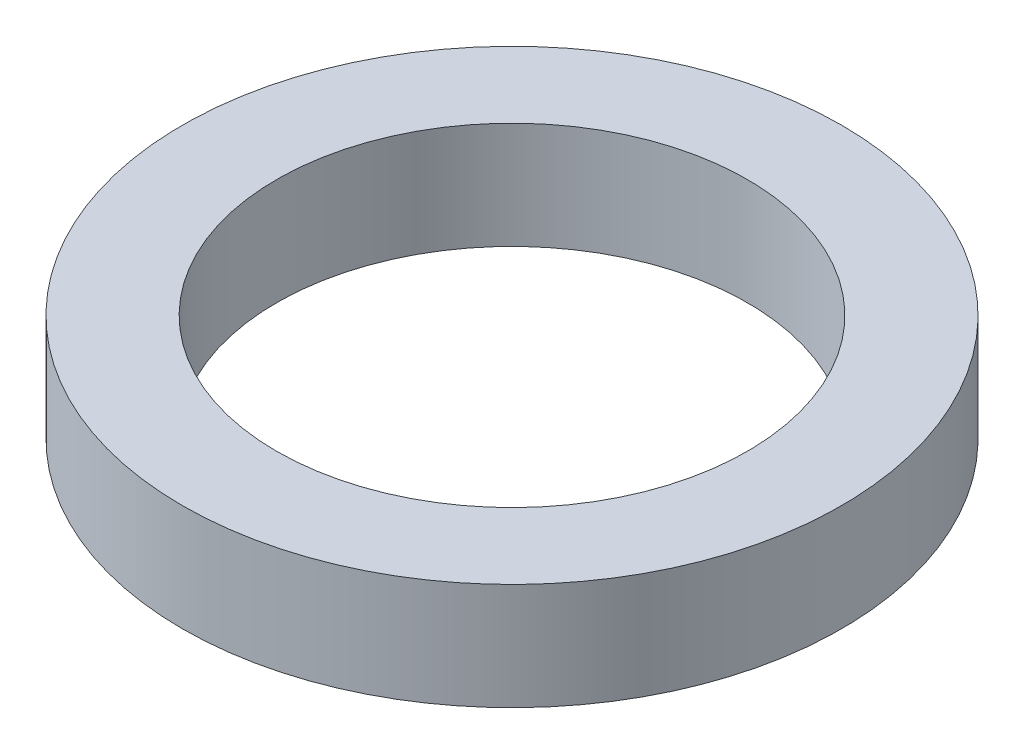
SolidWorks part; units mm, degrees
ref_plane "Front Plane" through (0, 0, 0) normal (0, 0, 1) x (1, 0, 0)
ref_plane "Top Plane" through (0, 0, 0) normal (0, 1, 0) x (1, 0, 0)
ref_plane "Right Plane" through (0, 0, 0) normal (1, 0, 0) x (0, 0, -1)
sketch "Sketch1" plane through (0, 0, 0) normal (0, 1, 0) x (1, 0, 0)
  circle A0 centre (0, 0) radius 52.5
  dimension "FLANGE_OD" = 105
extrude "Boss-Extrude1" add sketch "Sketch1" along normal blind 17
sketch "Sketch2" plane through (0, 0, 0) normal (0, 1, 0) x (1, 0, 0)
  circle A0 centre (0, 0) radius 37.5
  dimension "BORE_D" = 75
extrude "Cut-Extrude1" cut sketch "Sketch2" along normal through all
sketch "Sketch3" plane through (0, 17, 0) normal (0, 1, 0) x (1, 0, 0)
  circle A0 centre (0, 0) radius 21.9827 construction
  circle A1 centre (-21.9827, 0) radius 1.8661
  dimension "BOLT_D" = 3.7322
  dimension "BOLT_PCD" = 43.9655
extrude "Cut-Extrude2" cut sketch "Sketch3" against normal blind 13.5184 rebuild error yes
pattern_circular "CirPattern1" count 8 over 360 rebuild error yes
